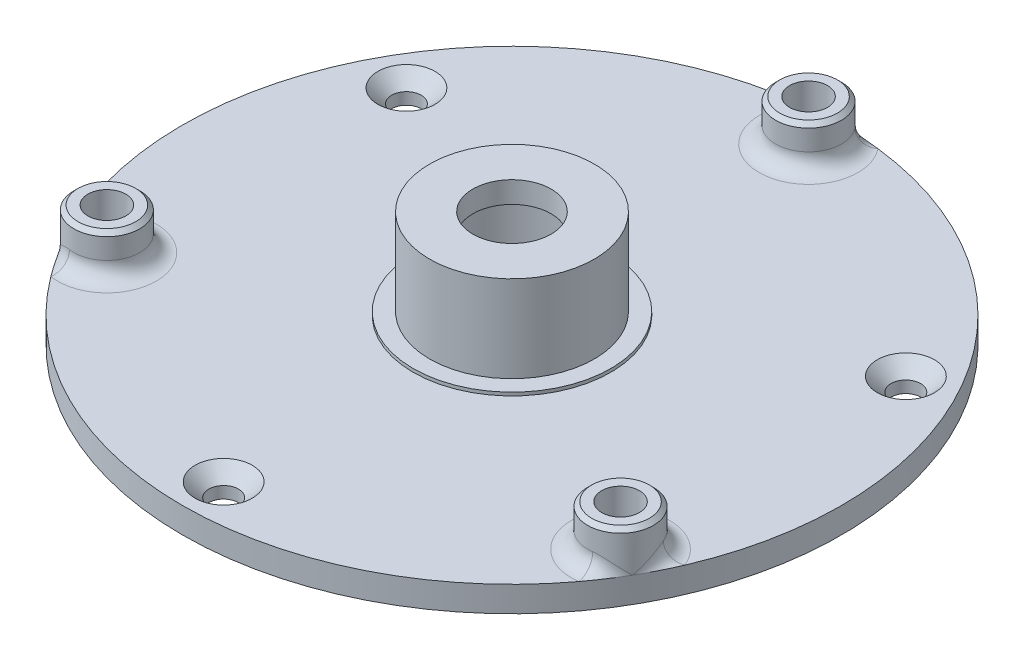
SolidWorks part; units mm, degrees
ref_plane "Płaszczyzna przednia" through (0, 0, 0) normal (0, 0, 1) x (1, 0, 0)
ref_plane "Płaszczyzna górna" through (0, 0, 0) normal (0, 1, 0) x (1, 0, 0)
ref_plane "Płaszczyzna prawa" through (0, 0, 0) normal (1, 0, 0) x (0, 0, -1)
sketch "Sketch1" plane through (0, 0, 0) normal (0, 1, 0) x (1, 0, 0)
  circle A0 centre (0, 0) radius 40
  dimension "D1" = 80
extrude "Boss-Extrude1" add sketch "Sketch1" along normal blind 3.5
sketch "Sketch2" plane through (0, 3.5, 0) normal (0, 1, 0) x (1, 0, 0)
  circle A0 centre (0, 0) radius 10
  dimension "D1" = 20
extrude "Boss-Extrude2" add sketch "Sketch2" along normal blind 12
sketch "Sketch3" plane through (0, 3.5, 0) normal (0, 1, 0) x (1, 0, 0)
  circle A0 centre (0, 0) radius 12
  circle A1 centre (0, 0) radius 40 construction
  circle A2 centre (0, 0) radius 40
  dimension "D1" = 24
extrude "Cut-Extrude1" cut sketch "Sketch3" against normal blind 0.4
sketch "Sketch5" plane through (0, 0, 0) normal (0, -1, 0) x (1, 0, 0)
  circle A0 centre (0, 0) radius 8
  dimension "D1" = 16
extrude "Cut-Extrude2" cut sketch "Sketch5" against normal blind 11
sketch "Sketch6" plane through (0, 15.5, 0) normal (0, 1, 0) x (1, 0, 0)
  circle A0 centre (0, 0) radius 4.75
  dimension "D1" = 9.5
extrude "Cut-Extrude3" cut sketch "Sketch6" against normal through all
sketch "Sketch7" plane through (0, 11, 0) normal (0, -1, 0) x (1, 0, 0)
  circle A0 centre (0, 0) radius 8 construction
  circle A1 centre (0, 0) radius 8 construction
  circle A2 centre (0, 0) radius 7
  circle A3 centre (0, 0) radius 4.75 construction
  circle A4 centre (0, 0) radius 4.75
  dimension "D1" = 1
extrude "Cut-Extrude4" cut sketch "Sketch7" against normal blind 0.4
sketch "Sketch8" plane through (0, 15.5, 0) normal (0, 1, 0) x (1, 0, 0)
  circle A1 centre (0, 0) radius 10
  circle A2 centre (0, 0) radius 10
  dimension "D1" = 0
extrude "Cut-Extrude5" cut sketch "Sketch8" against normal blind 1.5
sketch "Sketch9" plane through (0, 3.1, 0) normal (0, 1, 0) x (1, 0, 0)
  circle A0 centre (0, 0) radius 32 construction
  circle A1 centre (0, 36) radius 4
  circle A2 centre (31.1769, -18) radius 4
  circle A3 centre (-31.1769, -18) radius 4
  point P11 (0, 0)
  dimension "D1" = 64
  dimension "D2" = 8
  dimension "D3" = 3
extrude "Boss-Extrude3" add sketch "Sketch9" along normal blind 5
sketch "Sketch10" plane through (0, 8.1, 0) normal (0, 1, 0) x (1, 0, 0)
  circle A0 centre (0, 36) radius 2.3
  circle A1 centre (31.1769, -18) radius 2.3
  circle A2 centre (-31.1769, -18) radius 2.3
  circle A3 centre (0, 0) radius 36 construction
  point P9 (0, 0)
  dimension "D1" = 4.6
  dimension "D2" = 3
extrude "Cut-Extrude6" cut sketch "Sketch10" against normal through all
fillet "Fillet1" radius 2 3 edges at (31.1769, 3.1, 22) (-31.1769, 3.1, 22) (0, 3.1, -32)
chamfer "Chamfer1" distance 0.5 angle 45 3 edges at (31.1769, 8.1, 22) (-31.1769, 8.1, 22) (0, 8.1, -32)
hole_wizard "CSK for M3 Hex Socket Countersunk Head Screw1" positions "Sketch13" profile "Sketch14" countersink size "M3" standard "DIN" end condition through all
sketch "Sketch13" plane through (0, 3.1, 0) normal (0, 1, 0) x (1, 0, 0)
  circle A0 centre (0, 0) radius 35 construction
  point P6 (0, -35)
  point P11 (-30.3109, 17.5)
  point P12 (30.3109, 17.5)
  point P15 (0, 0)
  point P16 (0, -35)
  dimension "D1" = 3
  dimension "D2" = 70
sketch "Sketch14" plane through (30.3109, 3.1, -17.5) normal (1, 0, 0) x (0, 0, 1)
  line L0 (0, 0) -> (0, 3.1)
  line L1 (0, 3.1) -> (1.8, 3.1)
  line L2 (1.8, 3.1) -> (1.8, 1.67)
  line L3 (1.8, 1.67) -> (3.47, 0)
  line L5 (3.47, 0) -> (0, 0)
  line L6 (-1.8, 1.67) -> (-3.47, 0) construction
  line L11 (0, -6.35) -> (0, 107.95) construction
  dimension "Thru Hole Dia." = 3.6
  dimension "Thru Hole Depth" = 3.1
  dimension "Near C'Sink Dia." = 6.94
  dimension "Near C'Sink Angle" = 90
